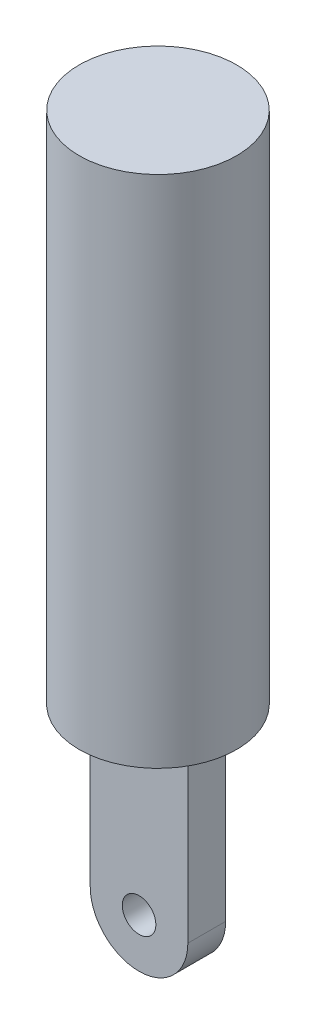
SolidWorks part; units mm, degrees
ref_plane "前视基准面" through (0, 0, 0) normal (0, 0, 1) x (1, 0, 0)
ref_plane "上视基准面" through (0, 0, 0) normal (0, 1, 0) x (1, 0, 0)
ref_plane "右视基准面" through (0, 0, 0) normal (1, 0, 0) x (0, 0, -1)
sketch "草图1" plane through (0, 0, 0) normal (0, 1, 0) x (1, 0, 0)
  circle A0 centre (0, 0) radius 9
  dimension "D1" = 18
extrude "凸台-拉伸1" add sketch "草图1" along normal blind 52
sketch "草图2" plane through (0, 52, 0) normal (0, 1, 0) x (1, 0, 0)
  circle A0 centre (0, 0) radius 7.8
  dimension "D1" = 15.6
extrude "凸台-拉伸2" add sketch "草图2" along normal blind 12
sketch "草图3" plane through (0, 0, 0) normal (0, 0, 1) x (1, 0, 0)
  line L0 (7.8, 64) -> (-7.8, 64) construction
  line L1 (-4.255, 59.5) -> (4.255, 59.5)
  line L2 (-4.255, 59.5) -> (-4.255, 68.5)
  line L4 (4.255, 59.5) -> (4.255, 68.5)
  line L5 (-4.255, 59.5) -> (4.255, 68.5) construction
  line L6 (-4.255, 68.5) -> (4.255, 59.5) construction
  arc A0 (-0.238, 64.2517) -> (0.238, 64.2517) centre (0, 68.5) ccw
  arc A1 (4.255, 68.5) -> (-4.255, 68.5) centre (0, 68.5) ccw
  circle A2 centre (0, 68.5) radius 2.6
  point P0 (0, 64)
  dimension "D2" = 5.2
  dimension "D1" = 8.51
extrude "凸台-拉伸3" add sketch "草图3" along normal blind 1.8 and the other way blind 1.8 contours L4 A1 L2 L1 A2 region at (0, 64.9997, 0)
sketch "草图4" plane through (0, 0, 0) normal (0, 0, 1) x (1, 0, 0)
  line L0 (0, 68.5) -> (0, -16.5) construction
  line L1 (-4.65, -16.5) -> (-4.65, -8.5)
  line L3 (4.65, -8.5) -> (4.65, -16.5)
  line L4 (-4.65, -8.5) -> (-4.65, 0)
  line L5 (-9, 0) -> (9, 0) construction
  line L6 (-4.65, 0) -> (4.65, 0)
  line L7 (4.65, 0) -> (4.65, -8.5)
  circle A0 centre (0, -16.5) radius 1.6
  arc A1 (-4.65, -16.5) -> (4.65, -16.5) centre (0, -16.5) ccw
  dimension "D1" = 3.2
  dimension "D2" = 9.3
extrude "凸台-拉伸4" add sketch "草图4" along normal blind 1.8 and the other way blind 1.8
sketch "草图5" plane through (0, 0, 0) normal (0, -1, 0) x (1, 0, 0)
  circle A0 centre (0, 0) radius 7.5
  circle A1 centre (0, 0) radius 12.4448
extrude "切除-拉伸1" cut sketch "草图5" against normal blind 75 and the other way blind 26
sketch "草图6" plane through (0, 64, 0) normal (0, 1, 0) x (1, 0, 0)
  circle A0 centre (0, 0) radius 11.5702
extrude "切除-拉伸2" cut sketch "草图6" against normal blind 15 and the other way blind 75
